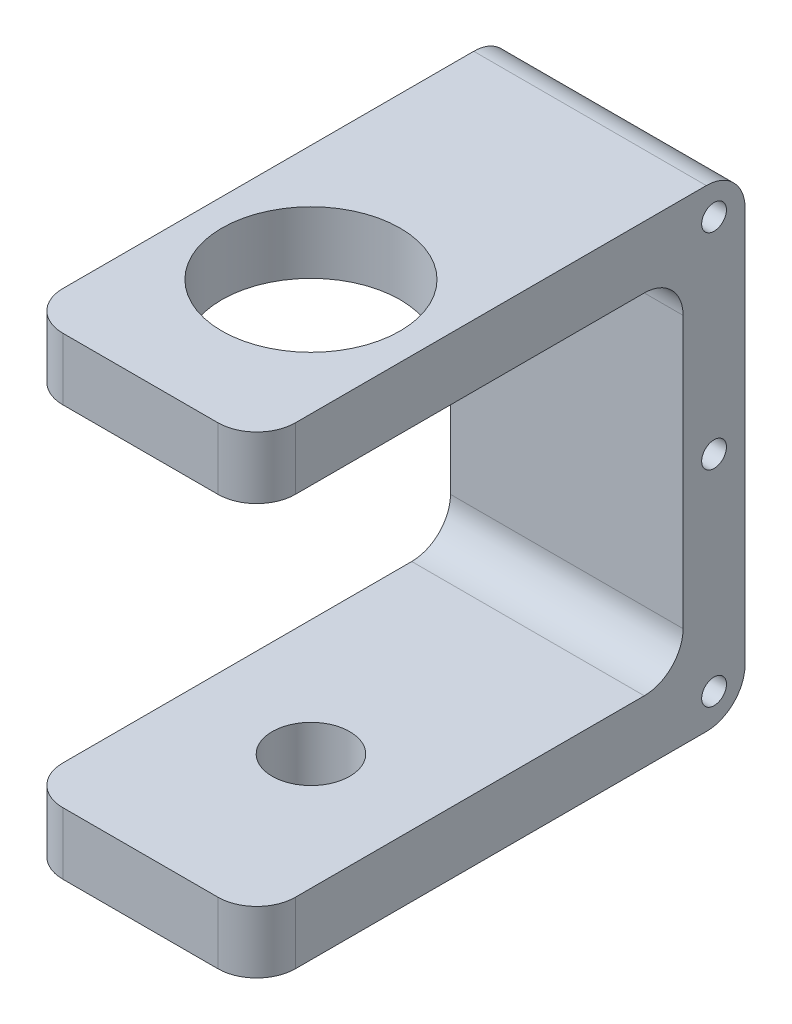
SolidWorks part; units mm, degrees
ref_plane "Front Plane" through (0, 0, 0) normal (0, 0, 1) x (1, 0, 0)
ref_plane "Top Plane" through (0, 0, 0) normal (0, 1, 0) x (1, 0, 0)
ref_plane "Right Plane" through (0, 0, 0) normal (1, 0, 0) x (0, 0, -1)
sketch "Sketch1" plane through (0, 0, 0) normal (1, 0, 0) x (0, 0, -1)
  line L0 (0, 0) -> (55, 0)
  line L1 (55, 0) -> (55, -45)
  line L2 (55, -45) -> (0, -45)
  line L3 (0, -45) -> (0, -53)
  line L4 (0, -53) -> (63, -53)
  line L5 (63, -53) -> (63, 8)
  line L6 (63, 8) -> (0, 8)
  line L7 (0, 8) -> (0, 0)
  dimension "D1" = 55
  dimension "D2" = 45
  dimension "D3" = 8
  dimension "D4" = 8
extrude "Boss-Extrude1" add sketch "Sketch1" along normal blind 30 contours L0 L1 L2 L3 L4 L5 L6 L7
sketch "Sketch2" plane through (0, 8, 0) normal (0, 1, 0) x (1, 0, 0)
  line L0 (30, 0) -> (0, 0) construction
  circle A0 centre (15, 22) radius 11.5
  point P2 (15, 0)
  dimension "D1" = 23
  dimension "D2" = 22
extrude "Cut-Extrude1" cut sketch "Sketch2" against normal up to next
sketch "Sketch3" plane through (0, -45, 0) normal (0, 1, 0) x (1, 0, 0)
  circle A0 centre (15, 22) radius 5
  circle A1 centre (15, 22) radius 11.5 construction
  dimension "D1" = 10
extrude "Cut-Extrude2" cut sketch "Sketch3" against normal up to next contours A0
sketch "Sketch4" plane through (30, 0, 0) normal (1, 0, 0) x (0, 0, -1)
  line L0 (63, -53) -> (63, 8) construction
  line L1 (55, 0) -> (55, -45) construction
  line L2 (0, 0) -> (55, 0) construction
  line L3 (55, -45) -> (0, -45) construction
  circle A0 centre (59, 4) radius 1.6
  circle A1 centre (59, -49) radius 1.6
  circle A2 centre (59, -22.5) radius 1.6
  point P6 (63, -22.5)
  dimension "D1" = 3.2
  dimension "D2" = 4
  dimension "D3" = 4
  dimension "D4" = 4
extrude "Cut-Extrude3" cut sketch "Sketch4" against normal up to next contours A2 | A1 | A0 region at (30, -49, -59) region at (30, -22.5, -59)
fillet "Fillet1" radius 5 6 edges at (15, -53, -63) (15, 8, -63) (0, -49, 0) (0, 4, 0) (30, -49, 0) (30, 4, 0)
fillet "Fillet2" radius 5 2 edges at (15, 0, -55) (15, -45, -55)
